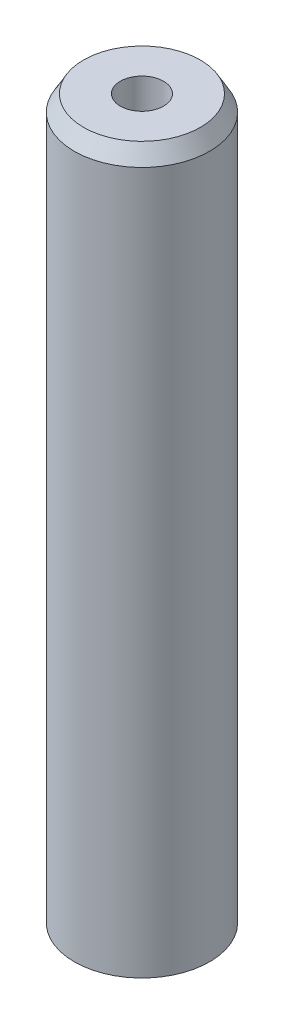
SolidWorks part; units mm, degrees
ref_plane "Front Plane" through (0, 0, 0) normal (0, 0, 1) x (1, 0, 0)
ref_plane "Top Plane" through (0, 0, 0) normal (0, 1, 0) x (1, 0, 0)
ref_plane "Right Plane" through (0, 0, 0) normal (1, 0, 0) x (0, 0, -1)
sketch "Sketch1" plane through (0, 0, 0) normal (0, 1, 0) x (1, 0, 0)
  circle A0 centre (0, 0) radius 20
  dimension "SHAFT_OD" = 40
extrude "Boss-Extrude1" add sketch "Sketch1" along normal blind 214.9385
sketch "Sketch2" plane through (0, 0, 0) normal (0, 1, 0) x (1, 0, 0)
  circle A0 centre (0, 0) radius 6.387
  dimension "BORE_D" = 12.7739
extrude "Cut-Extrude1" cut sketch "Sketch2" along normal through all
chamfer "Chamfer1" distance 4.7507 angle 30 2 edges at (0, 214.9385, 20) (0, 0, 20) first distance on face at (0, 214.9385, 20) first distance on face at (0, 0, 6.387)
